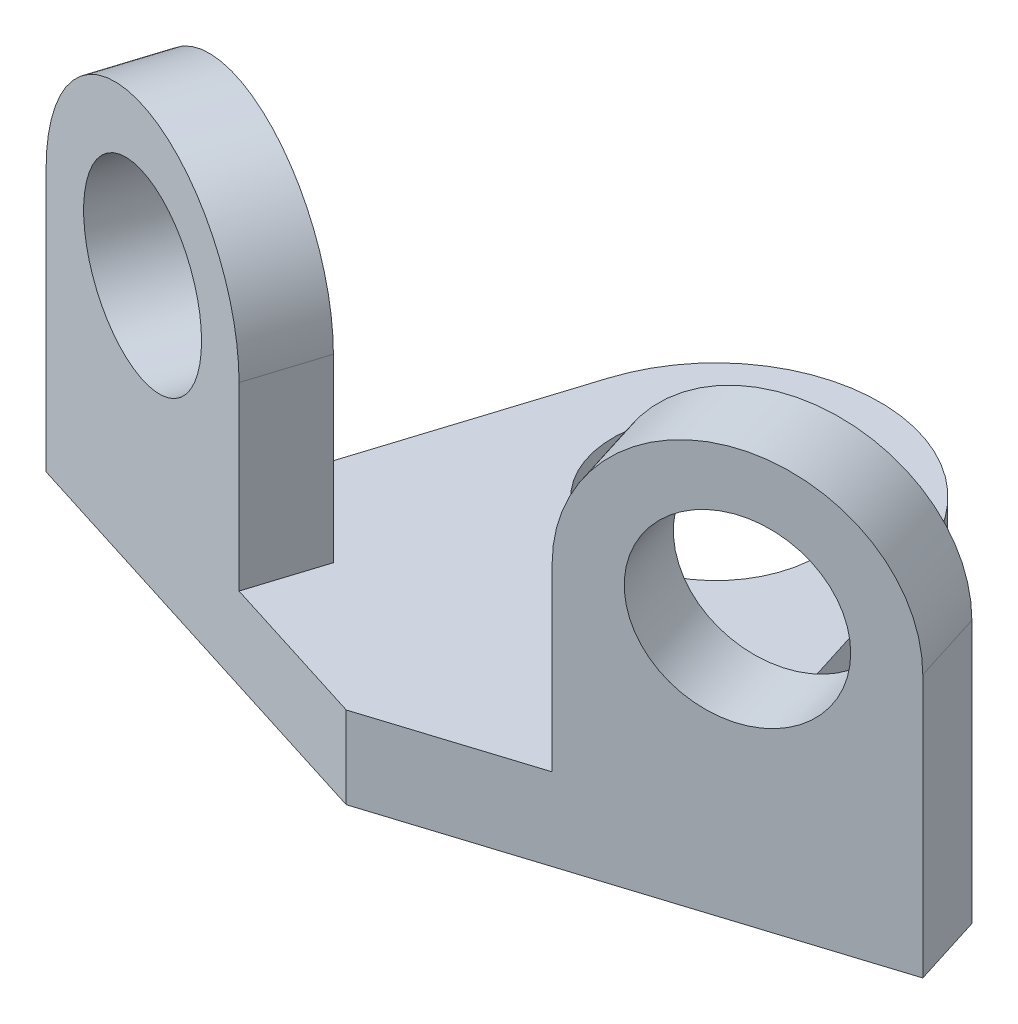
SolidWorks part; units mm, degrees
ref_plane "Front Plane" through (0, 0, 0) normal (0, 0, 1) x (1, 0, 0)
ref_plane "Top Plane" through (0, 0, 0) normal (0, 1, 0) x (1, 0, 0)
ref_plane "Right Plane" through (0, 0, 0) normal (1, 0, 0) x (0, 0, -1)
sketch "Sketch2" plane through (0, 0, 0) normal (0, 1, 0) x (1, 0, 0)
  line L0 (0, 0) -> (53.4081, 16.8395)
  line L2 (72.0703, 0) -> (-84.7973, 0) construction
  line L3 (-19.0451, 51.0141) -> (-29.1979, 18.8137)
  line L4 (19.499, 49.5748) -> (29.1979, 18.8137)
  line L5 (0, 101.52) -> (0, -31.3735) construction
  line L6 (53.4081, 16.8395) -> (50.6528, 25.5784)
  line L7 (50.6528, 25.5784) -> (16.319, 14.753)
  line L8 (16.319, 14.753) -> (19.0743, 6.0141)
  line L9 (-53.4081, 16.8395) -> (-50.6528, 25.5784)
  line L10 (0, 0) -> (-53.4081, 16.8395)
  line L11 (-16.319, 14.753) -> (-19.0743, 6.0141)
  line L12 (-50.6528, 25.5784) -> (-16.319, 14.753)
  circle A0 centre (0.0292, 45) radius 12.5
  arc A1 (19.499, 49.5748) -> (-19.0451, 51.0141) centre (0.0292, 45) ccw
  dimension "D2" = 45
  dimension "D3" = 35
  dimension "D1" = 20
extrude "Boss-Extrude1" add sketch "Sketch2" along normal blind 10 contours L4 A1 L3 L12 L11 L10 L0 L8 L7 A0 region at (-0.0009, 0, -28.7996)
extrude "Boss-Extrude2" add sketch "Sketch2<4>" along normal blind 50 contours L7 L8 L0 L6 | L12 L9 L10 L11 region at (34.8636, 0, -15.7962) region at (-34.8636, 0, -15.7962)
sketch "Sketch2<4>" plane through (0, 0, 0) normal (0, 1, 0) x (1, 0, 0) same geometry as "Sketch2"
sketch "Sketch3" plane through (0, 0, 0) normal (-0.3007, 0, 0.9537) x (0.9537, 0, 0.3007)
  line L1 (0, 0) -> (-56, 0) construction
  line L2 (-56, 50) -> (-56, 0) construction
  line L3 (-11.9039, 32) -> (-67.252, 32) construction
  circle A0 centre (-38, 32) radius 11
  arc A1 (-20, 32) -> (-56, 32) centre (-38, 32) ccw
  line M4 (-20, 10) -> (-20, 50)
  line M5 (-20, 50) -> (-56, 50)
  line M6 (-56, 50) -> (-56, 0)
  dimension "D1" = 32
  dimension "D2" = 18
sketch "Sketch5" plane through (0, 0, 0) normal (0.3007, 0, 0.9537) x (0.9537, 0, -0.3007)
  line L1 (56, 50) -> (56, 0) construction
  line L2 (56, 32) -> (54.9644, 32) construction
  circle A0 centre (38, 32) radius 11
  arc A1 (56, 32) -> (20, 32) centre (38, 32) ccw
  line M2 (56, 0) -> (56, 50)
  line M3 (56, 50) -> (20, 50)
  line M4 (20, 50) -> (20, 10)
  dimension "D2" = 18
extrude "Cut-Extrude3" cut sketch "Sketch5" against normal blind 20 contours A0 | A1 M2 M3 | A1 M3 M4 region at (36.2412, 32, -11.4268) region at (22.9089, 45.9794, -7.2231) region at (49.5736, 45.9794, -15.6305)
extrude "Cut-Extrude4" cut sketch "Sketch3" against normal blind 20 contours L3 A0 | A0 L3 | A1 M4 M5 | A1 M5 M6 region at (-22.9089, 45.9794, -7.2231) region at (-36.2412, 27.3315, -11.4268) region at (-36.2412, 36.6685, -11.4268) region at (-49.5736, 45.9794, -15.6305)
